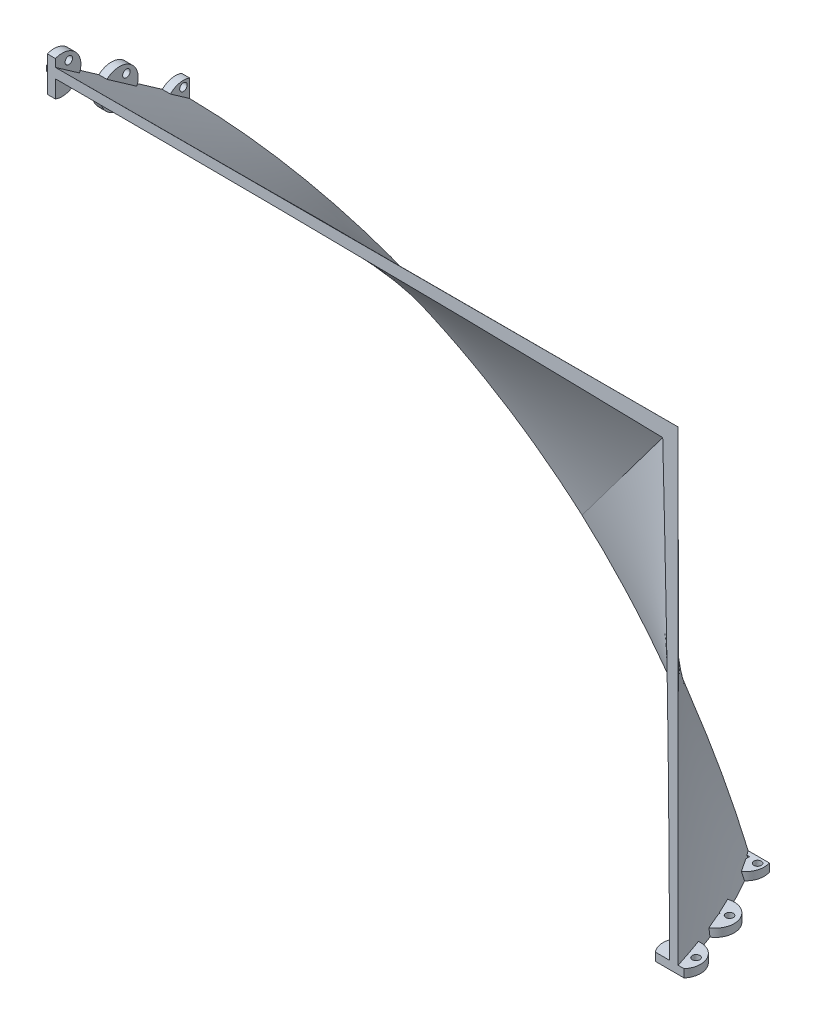
SolidWorks part; units mm, degrees
ref_plane "Plan de face" through (0, 0, 0) normal (0, 0, 1) x (1, 0, 0)
ref_plane "Plan de dessus" through (0, 0, 0) normal (0, 1, 0) x (1, 0, 0)
ref_plane "Plan de droite" through (0, 0, 0) normal (1, 0, 0) x (0, 0, -1)
ref_plane "Plan1" through (0, 0, 10) normal (0, 0, 1) x (1, 0, 0)
ref_plane "Plan2" through (0, 0, 60) normal (0, 0, 1) x (1, 0, 0)
sketch "Esquisse1" plane through (0, 0, 60) normal (0, 0, 1) x (1, 0, 0)
  line L1 (-235, -265) -> (235, -265)
  line L2 (-235, -265) -> (-235, 265)
  line L3 (-235, 265) -> (235, 265)
  line L4 (235, -265) -> (235, 265)
  line L5 (-235, -265) -> (235, 265) construction
  line L6 (-235, 265) -> (235, -265) construction
  point P0 (0, 0)
  dimension "D1" = 470
  dimension "D2" = 530
sketch "Esquisse2" plane through (0, 0, 10) normal (0, 0, 1) x (1, 0, 0)
  circle A0 centre (0, 0) radius 230
loft "Lissage1" add profiles "Esquisse2", "Esquisse1" connector at (-217.3645, 75.1842, 10) connector at (-235, 265, 60)
shell "Coque1" thickness 3 removed face at (0, 0, 60)
sketch "Esquisse3" plane through (0, 0, 13) normal (0, 0, 1) x (1, 0, 0)
  spline S4 degree 3 poles (-1744.7327, 376.1903) (-526.9338, -261.2431) (-3.804, -346.9049) (174.7035, -148.6101) (179.7346, -142.3812) (189.1199, -129.386) (193.4749, -122.6201) (198.4789, -113.8135) (199.4591, -112.0321) (201.3646, -108.4534) (202.2908, -106.6549) (204.9907, -101.232) (206.6856, -97.5804) (211.4617, -86.5187) (214.236, -79.0024) (218.9895, -63.6942) (220.9703, -55.9031) (222.9555, -45.9941) (223.3279, -44.0038) (224.0237, -40.0062) (224.3459, -38.0049) (225.2353, -32.0028) (225.7261, -28) (226.8998, -15.9875) (227.2865, -7.9737) (227.2836, 8.0646) (226.894, 16.0892) (225.9081, 26.1268) (225.6858, 28.1347) (225.1902, 32.1512) (224.9166, 34.1622) (224.021, 40.178) (223.3259, 44.156) (220.9479, 55.9928) (218.9722, 63.7545) (214.2305, 79.0156) (211.4628, 86.5145) (206.6954, 97.5584) (205.0032, 101.2055) (202.3067, 106.6237) (201.3815, 108.421) (199.4777, 111.9979) (198.4976, 113.78) (193.4909, 122.5945) (189.1338, 129.3656) (179.7439, 142.3695) (174.7107, 148.6017) (-4.1787, 347.3344) (-528.7451, 260.2995) (-1744.2878, -377.4815) knots -1.953743 -1.953743 -1.953743 -1.953743 0.0625 0.0625 0.125 0.125 0.1875 0.1875 0.203125 0.203125 0.21875 0.21875 0.25 0.25 0.3125 0.3125 0.375 0.375 0.390625 0.390625 0.40625 0.40625 0.4375 0.4375 0.5 0.5 0.5625 0.5625 0.578125 0.578125 0.59375 0.59375 0.625 0.625 0.6875 0.6875 0.75 0.75 0.78125 0.78125 0.796875 0.796875 0.8125 0.8125 0.875 0.875 0.9375 0.9375 2.957415 2.957415 2.957415 2.957415 only from (152.2162, -171.6485) to (152.2162, 171.6485)
  spline S5 degree 3 poles (-195.2618, -1771.3819) (316.1646, -491.0086) (344.6975, 32.7076) (130.3839, 188.7229) (124.6273, 192.5237) (112.7752, 199.5943) (106.68, 202.8645) (98.8449, 206.6138) (97.2671, 207.3467) (94.0897, 208.7785) (92.4898, 209.4774) (87.681, 211.5127) (84.4552, 212.7913) (74.7194, 216.3971) (68.1511, 218.4952) (54.8632, 222.0955) (48.1436, 223.5983) (34.5539, 226.0114) (27.684, 226.9224) (19.0006, 227.6836) (17.263, 227.8166) (13.7931, 228.0438) (12.0597, 228.1381) (6.8641, 228.3641) (3.4064, 228.4387) (-6.9486, 228.4367) (-13.828, 228.1355) (-27.5391, 226.9367) (-34.3709, 226.0386) (-44.5819, 224.2333) (-47.9794, 223.5547) (-53.0663, 222.4195) (-54.7604, 222.0216) (-58.1454, 221.1859) (-59.8336, 220.7489) (-68.2258, 218.4749) (-74.8099, 216.3655) (-87.7243, 211.5786) (-94.0544, 208.9004) (-106.4603, 202.9753) (-112.536, 199.7278) (-121.4549, 194.4207) (-124.3952, 192.5788) (-128.7561, 189.7046) (-130.2026, 188.7271) (-133.0695, 186.7413) (-134.4907, 185.7324) (-375.502, 10.4249) (-260.223, -622.6751) (244.4446, -1759.2058) knots -2.272579 -2.272579 -2.272579 -2.272579 0.0625 0.0625 0.125 0.125 0.1875 0.1875 0.203125 0.203125 0.21875 0.21875 0.25 0.25 0.3125 0.3125 0.375 0.375 0.4375 0.4375 0.453125 0.453125 0.46875 0.46875 0.5 0.5 0.5625 0.5625 0.625 0.625 0.65625 0.65625 0.671875 0.671875 0.6875 0.6875 0.75 0.75 0.8125 0.8125 0.875 0.875 0.90625 0.90625 0.921875 0.921875 0.9375 0.9375 3.594862 3.594862 3.594862 3.594862 only from (152.2162, 171.6485) to (-152.2162, 171.6485)
  spline S6 degree 3 poles (1744.7327, -376.1903) (526.9338, 261.2431) (3.804, 346.9049) (-174.7035, 148.6101) (-179.7346, 142.3812) (-189.1199, 129.386) (-193.4749, 122.6201) (-198.4789, 113.8135) (-199.4591, 112.0321) (-201.3646, 108.4534) (-202.2908, 106.6549) (-204.9907, 101.232) (-206.6856, 97.5804) (-211.4617, 86.5187) (-214.236, 79.0024) (-218.9895, 63.6942) (-220.9703, 55.9031) (-222.9555, 45.9941) (-223.3279, 44.0038) (-224.0237, 40.0062) (-224.3459, 38.0049) (-225.2353, 32.0028) (-225.7261, 28) (-226.8998, 15.9875) (-227.2865, 7.9737) (-227.2836, -8.0646) (-226.894, -16.0892) (-225.9081, -26.1268) (-225.6858, -28.1347) (-225.1902, -32.1512) (-224.9166, -34.1622) (-224.021, -40.178) (-223.3259, -44.156) (-220.9479, -55.9928) (-218.9722, -63.7545) (-214.2305, -79.0156) (-211.4628, -86.5145) (-206.6954, -97.5584) (-205.0032, -101.2055) (-202.3067, -106.6237) (-201.3815, -108.421) (-199.4777, -111.9979) (-198.4976, -113.78) (-193.4909, -122.5945) (-189.1338, -129.3656) (-179.7439, -142.3695) (-174.7107, -148.6017) (4.1787, -347.3344) (528.7451, -260.2995) (1744.2878, 377.4815) knots -1.953743 -1.953743 -1.953743 -1.953743 0.0625 0.0625 0.125 0.125 0.1875 0.1875 0.203125 0.203125 0.21875 0.21875 0.25 0.25 0.3125 0.3125 0.375 0.375 0.390625 0.390625 0.40625 0.40625 0.4375 0.4375 0.5 0.5 0.5625 0.5625 0.578125 0.578125 0.59375 0.59375 0.625 0.625 0.6875 0.6875 0.75 0.75 0.78125 0.78125 0.796875 0.796875 0.8125 0.8125 0.875 0.875 0.9375 0.9375 2.957415 2.957415 2.957415 2.957415 only from (-152.2162, 171.6485) to (-152.2162, -171.6485)
  spline S7 degree 3 poles (195.2618, 1771.3819) (-316.1646, 491.0086) (-344.6975, -32.7076) (-130.3839, -188.7229) (-124.6273, -192.5237) (-112.7752, -199.5943) (-106.68, -202.8645) (-98.8449, -206.6138) (-97.2671, -207.3467) (-94.0897, -208.7785) (-92.4898, -209.4774) (-87.681, -211.5127) (-84.4552, -212.7913) (-74.7194, -216.3971) (-68.1511, -218.4952) (-54.8632, -222.0955) (-48.1436, -223.5983) (-34.5539, -226.0114) (-27.684, -226.9224) (-19.0006, -227.6836) (-17.263, -227.8166) (-13.7931, -228.0438) (-12.0597, -228.1381) (-6.8641, -228.3641) (-3.4064, -228.4387) (6.9486, -228.4367) (13.828, -228.1355) (27.5391, -226.9367) (34.3709, -226.0386) (44.5819, -224.2333) (47.9794, -223.5547) (53.0663, -222.4195) (54.7604, -222.0216) (58.1454, -221.1859) (59.8336, -220.7489) (68.2258, -218.4749) (74.8099, -216.3655) (87.7243, -211.5786) (94.0544, -208.9004) (106.4603, -202.9753) (112.536, -199.7278) (121.4549, -194.4207) (124.3952, -192.5788) (128.7561, -189.7046) (130.2026, -188.7271) (133.0695, -186.7413) (134.4907, -185.7324) (375.502, -10.4249) (260.223, 622.6751) (-244.4446, 1759.2058) knots -2.272579 -2.272579 -2.272579 -2.272579 0.0625 0.0625 0.125 0.125 0.1875 0.1875 0.203125 0.203125 0.21875 0.21875 0.25 0.25 0.3125 0.3125 0.375 0.375 0.4375 0.4375 0.453125 0.453125 0.46875 0.46875 0.5 0.5 0.5625 0.5625 0.625 0.625 0.65625 0.65625 0.671875 0.671875 0.6875 0.6875 0.75 0.75 0.8125 0.8125 0.875 0.875 0.90625 0.90625 0.921875 0.921875 0.9375 0.9375 3.594862 3.594862 3.594862 3.594862 only from (-152.2162, -171.6485) to (152.2162, -171.6485)
  spline S8 degree 3 poles (152.2162, -171.6485) (158.2661, -166.2289) (163.9694, -160.534) (174.7035, -148.6101) (179.7346, -142.3812) (189.1199, -129.386) (193.4749, -122.6201) (198.4789, -113.8135) (199.4591, -112.0321) (201.3646, -108.4534) (202.2908, -106.6549) (204.9907, -101.232) (206.6856, -97.5804) (211.4617, -86.5187) (214.236, -79.0024) (218.9895, -63.6942) (220.9703, -55.9031) (222.9555, -45.9941) (223.3279, -44.0038) (224.0237, -40.0062) (224.3459, -38.0049) (225.2353, -32.0028) (225.7261, -28) (226.8998, -15.9875) (227.2865, -7.9737) (227.2836, 8.0646) (226.894, 16.0892) (225.9081, 26.1268) (225.6858, 28.1347) (225.1902, 32.1512) (224.9166, 34.1622) (224.021, 40.178) (223.3259, 44.156) (220.9479, 55.9928) (218.9722, 63.7545) (214.2305, 79.0156) (211.4628, 86.5145) (206.6954, 97.5584) (205.0032, 101.2055) (202.3067, 106.6237) (201.3815, 108.421) (199.4777, 111.9979) (198.4976, 113.78) (193.4909, 122.5945) (189.1338, 129.3656) (179.7439, 142.3695) (174.7107, 148.6017) (163.9726, 160.5309) (158.2675, 166.2277) (152.2162, 171.6485) knots 0 0 0 0 0.0625 0.0625 0.125 0.125 0.1875 0.1875 0.203125 0.203125 0.21875 0.21875 0.25 0.25 0.3125 0.3125 0.375 0.375 0.390625 0.390625 0.40625 0.40625 0.4375 0.4375 0.5 0.5 0.5625 0.5625 0.578125 0.578125 0.59375 0.59375 0.625 0.625 0.6875 0.6875 0.75 0.75 0.78125 0.78125 0.796875 0.796875 0.8125 0.8125 0.875 0.875 0.9375 0.9375 1 1 1 1
  spline S9 degree 3 poles (152.2162, 171.6485) (146.9741, 176.2555) (141.5573, 180.5889) (130.3839, 188.7229) (124.6273, 192.5237) (112.7752, 199.5943) (106.68, 202.8645) (98.8449, 206.6138) (97.2671, 207.3467) (94.0897, 208.7785) (92.4898, 209.4774) (87.681, 211.5127) (84.4552, 212.7913) (74.7194, 216.3971) (68.1511, 218.4952) (54.8632, 222.0955) (48.1436, 223.5983) (34.5539, 226.0114) (27.684, 226.9224) (19.0006, 227.6836) (17.263, 227.8166) (13.7931, 228.0438) (12.0597, 228.1381) (6.8641, 228.3641) (3.4064, 228.4387) (-6.9486, 228.4367) (-13.828, 228.1355) (-27.5391, 226.9367) (-34.3709, 226.0386) (-44.5819, 224.2333) (-47.9794, 223.5547) (-53.0663, 222.4195) (-54.7604, 222.0216) (-58.1454, 221.1859) (-59.8336, 220.7489) (-68.2258, 218.4749) (-74.8099, 216.3655) (-87.7243, 211.5786) (-94.0544, 208.9004) (-106.4603, 202.9753) (-112.536, 199.7278) (-121.4549, 194.4207) (-124.3952, 192.5788) (-128.7561, 189.7046) (-130.2026, 188.7271) (-133.0695, 186.7413) (-134.4907, 185.7324) (-141.5348, 180.6086) (-146.9739, 176.2557) (-152.2162, 171.6485) knots 0 0 0 0 0.0625 0.0625 0.125 0.125 0.1875 0.1875 0.203125 0.203125 0.21875 0.21875 0.25 0.25 0.3125 0.3125 0.375 0.375 0.4375 0.4375 0.453125 0.453125 0.46875 0.46875 0.5 0.5 0.5625 0.5625 0.625 0.625 0.65625 0.65625 0.671875 0.671875 0.6875 0.6875 0.75 0.75 0.8125 0.8125 0.875 0.875 0.90625 0.90625 0.921875 0.921875 0.9375 0.9375 1 1 1 1
  spline S10 degree 3 poles (-152.2162, 171.6485) (-158.2661, 166.2289) (-163.9694, 160.534) (-174.7035, 148.6101) (-179.7346, 142.3812) (-189.1199, 129.386) (-193.4749, 122.6201) (-198.4789, 113.8135) (-199.4591, 112.0321) (-201.3646, 108.4534) (-202.2908, 106.6549) (-204.9907, 101.232) (-206.6856, 97.5804) (-211.4617, 86.5187) (-214.236, 79.0024) (-218.9895, 63.6942) (-220.9703, 55.9031) (-222.9555, 45.9941) (-223.3279, 44.0038) (-224.0237, 40.0062) (-224.3459, 38.0049) (-225.2353, 32.0028) (-225.7261, 28) (-226.8998, 15.9875) (-227.2865, 7.9737) (-227.2836, -8.0646) (-226.894, -16.0892) (-225.9081, -26.1268) (-225.6858, -28.1347) (-225.1902, -32.1512) (-224.9166, -34.1622) (-224.021, -40.178) (-223.3259, -44.156) (-220.9479, -55.9928) (-218.9722, -63.7545) (-214.2305, -79.0156) (-211.4628, -86.5145) (-206.6954, -97.5584) (-205.0032, -101.2055) (-202.3067, -106.6237) (-201.3815, -108.421) (-199.4777, -111.9979) (-198.4976, -113.78) (-193.4909, -122.5945) (-189.1338, -129.3656) (-179.7439, -142.3695) (-174.7107, -148.6017) (-163.9726, -160.5309) (-158.2675, -166.2277) (-152.2162, -171.6485) knots 0 0 0 0 0.0625 0.0625 0.125 0.125 0.1875 0.1875 0.203125 0.203125 0.21875 0.21875 0.25 0.25 0.3125 0.3125 0.375 0.375 0.390625 0.390625 0.40625 0.40625 0.4375 0.4375 0.5 0.5 0.5625 0.5625 0.578125 0.578125 0.59375 0.59375 0.625 0.625 0.6875 0.6875 0.75 0.75 0.78125 0.78125 0.796875 0.796875 0.8125 0.8125 0.875 0.875 0.9375 0.9375 1 1 1 1
  spline S11 degree 3 poles (-152.2162, -171.6485) (-146.9741, -176.2555) (-141.5573, -180.5889) (-130.3839, -188.7229) (-124.6273, -192.5237) (-112.7752, -199.5943) (-106.68, -202.8645) (-98.8449, -206.6138) (-97.2671, -207.3467) (-94.0897, -208.7785) (-92.4898, -209.4774) (-87.681, -211.5127) (-84.4552, -212.7913) (-74.7194, -216.3971) (-68.1511, -218.4952) (-54.8632, -222.0955) (-48.1436, -223.5983) (-34.5539, -226.0114) (-27.684, -226.9224) (-19.0006, -227.6836) (-17.263, -227.8166) (-13.7931, -228.0438) (-12.0597, -228.1381) (-6.8641, -228.3641) (-3.4064, -228.4387) (6.9486, -228.4367) (13.828, -228.1355) (27.5391, -226.9367) (34.3709, -226.0386) (44.5819, -224.2333) (47.9794, -223.5547) (53.0663, -222.4195) (54.7604, -222.0216) (58.1454, -221.1859) (59.8336, -220.7489) (68.2258, -218.4749) (74.8099, -216.3655) (87.7243, -211.5786) (94.0544, -208.9004) (106.4603, -202.9753) (112.536, -199.7278) (121.4549, -194.4207) (124.3952, -192.5788) (128.7561, -189.7046) (130.2026, -188.7271) (133.0695, -186.7413) (134.4907, -185.7324) (141.5348, -180.6086) (146.9739, -176.2557) (152.2162, -171.6485) knots 0 0 0 0 0.0625 0.0625 0.125 0.125 0.1875 0.1875 0.203125 0.203125 0.21875 0.21875 0.25 0.25 0.3125 0.3125 0.375 0.375 0.4375 0.4375 0.453125 0.453125 0.46875 0.46875 0.5 0.5 0.5625 0.5625 0.625 0.625 0.65625 0.65625 0.671875 0.671875 0.6875 0.6875 0.75 0.75 0.8125 0.8125 0.875 0.875 0.90625 0.90625 0.921875 0.921875 0.9375 0.9375 1 1 1 1
  dimension "D1" = 0
extrude "Enlèv. mat.-Extru.1" cut sketch "Esquisse3" against normal blind 10
sketch "Esquisse4" plane through (0, 0, 0) normal (0, 1, 0) x (1, 0, 0)
  line L0 (-55, -10) -> (55, -10) construction
  line L1 (-235, -10) -> (235, -10)
  line L2 (-235, -10) -> (-235, -60)
  line L3 (-235, -60) -> (235, -60)
  line L4 (235, -10) -> (235, -60)
  line L5 (-55, -60) -> (55, -60) construction
  line L6 (0, -10) -> (0, -60)
  point P10 (0, -60)
  point P13 (0, -10)
extrude "Enlèv. mat.-Extru.2" cut sketch "Esquisse4" against normal through all both and the other way through all contours L6 L1 L2 L3 region at (-117.5, 0, 35)
sketch "Esquisse7" plane through (0, 0, 0) normal (0, 0, 1) x (1, 0, 0)
  line L0 (0, -88.3333) -> (235, -88.3333)
  line L1 (0, 261.338) -> (235, 261.338)
  line L2 (0, 261.338) -> (0, -265)
  line L3 (0, -265) -> (235, -265)
  line L4 (235, 261.338) -> (235, -265)
  line L5 (0, 88.3333) -> (235, 88.3333)
  dimension "D1" = 176.6667
  dimension "D2" = 176.6667
extrude "Enlèv. mat.-Extru.3" cut sketch "Esquisse7" against normal through all both and the other way through all contours L4 L0 L2 L3 | L5 L2 L0 L4 region at (117.5, 0, 0) region at (117.5, -176.6667, 0)
sketch "Esquisse8" plane through (0, 88.3333, 0) normal (0, -1, 0) x (1, 0, 0)
  line L0 (225, 36.15) -> (225, 60) construction
  line L1 (224, 35.4) -> (226, 35.4)
  line L2 (224, 35.4) -> (224, 36.9)
  line L3 (224, 36.9) -> (226, 36.9)
  line L4 (226, 35.4) -> (226, 36.9)
  line L5 (224, 35.4) -> (226, 36.9) construction
  line L6 (224, 36.9) -> (226, 35.4) construction
  line L7 (97.1744, 60) -> (-97.1744, 60) construction
  line L8 (225, 60) -> (235, 60) construction
  line L10 (235, 60) -> (235, 36.15) construction
  line L11 (231.8645, 55.5) -> (235.8645, 55.5) construction
  line L12 (231.8645, 60) -> (231.8645, 55.5) construction
  line L13 (212.361, 10) -> (212.361, 12.3) construction
  line L14 (205.7497, 10) -> (218.9724, 10)
  line L15 (230.8645, 54.75) -> (232.8645, 54.75)
  line L16 (230.8645, 54.75) -> (230.8645, 56.25)
  line L17 (230.8645, 56.25) -> (232.8645, 56.25)
  line L18 (232.8645, 54.75) -> (232.8645, 56.25)
  line L19 (230.8645, 54.75) -> (232.8645, 56.25) construction
  line L20 (230.8645, 56.25) -> (232.8645, 54.75) construction
  line L21 (211.461, 11.65) -> (213.261, 11.65)
  line L22 (211.461, 11.65) -> (211.461, 12.95)
  line L23 (211.461, 12.95) -> (213.261, 12.95)
  line L24 (213.261, 11.65) -> (213.261, 12.95)
  line L25 (211.461, 11.65) -> (213.261, 12.95) construction
  line L26 (211.461, 12.95) -> (213.261, 11.65) construction
  line L27 (152.2162, 10) -> (210.59, 10) construction
  line L28 (97.1744, 10) -> (-97.1744, 10) construction
  line L29 (226.5026, 60) -> (237.2264, 60)
  line L30 (238.3714, 53.3767) -> (225.0703, 57.7448) construction
  line L31 (235, 60) -> (231.2328, 48.5286) construction
  line L32 (230.9261, 33.3126) -> (218.0536, 38.8171) construction
  line L33 (228.8555, 41.9925) -> (223.4391, 29.3262) construction
  line L34 (217.1315, 17.4228) -> (212.361, 10) construction
  line L35 (212.361, 12.3) -> (216.891, 12.3) construction
  line L36 (225, 36.15) -> (228.5, 36.15) construction
  line L37 (228.5, 36.15) -> (228.5, 34.35) construction
  line L38 (235.8645, 55.5) -> (235.8645, 54.2) construction
  arc A0 (226.5026, 60) -> (237.2264, 60) centre (231.8645, 55.5) ccw
  circle A1 centre (225, 36.15) radius 7
  arc A2 (218.9724, 10) -> (205.7497, 10) centre (212.361, 12.3) ccw
  arc A3 (205.7497, 10) -> (218.9724, 10) centre (212.361, 12.3) ccw construction
  arc A4 (237.2264, 60) -> (226.5026, 60) centre (231.8645, 55.5) ccw construction
  circle A5 centre (235.8645, 54.2) radius 1.4
  circle A6 centre (228.5, 34.35) radius 1.4
  circle A7 centre (216.891, 12.3) radius 1.4
  spline S0 degree 3 poles (212.361, 10) (214.9908, 13.7747) (217.3789, 17.6908) (220.6719, 23.734) (221.7217, 25.7777) (223.733, 29.9109) (225.6529, 34.0835) (227.4125, 38.3253) (229.1017, 42.5976) (229.9111, 44.7493) (232.2428, 51.2344) (233.6703, 55.6006) (235, 60) knots 0 0 0 0 0.25 0.25 0.375 0.375 0.5 0.625 0.625 0.75 0.75 1 1 1 1 construction
  point P0 (225, 36.15)
  point P41 (231.2328, 48.5286)
  point P42 (223.4391, 29.3262)
  point P51 (228.8555, 41.9925)
  point P59 (216.8065, 17.7072)
  dimension "D11" = 4
  dimension "D12" = 2.8
  dimension "D14" = 2.8
  dimension "D16" = 2.8
  dimension "D17" = 4.53
  dimension "D1" = 2
  dimension "D2" = 1.5
  dimension "D3" = 23.85
  dimension "D4" = 10
  dimension "D6" = 4.5
  dimension "D7" = 1.8
  dimension "D8" = 1.3
  dimension "D9" = 2
  dimension "D10" = 1.5
  dimension "D13" = 3.5
  dimension "D15" = 1.8
  dimension "D18" = 1.3
extrude "Boss.-Extru.1" add sketch "Esquisse8" along normal blind 2 contours L22 L21 L24 L23 | L2 L1 L4 L3 | L16 L15 L18 L17
sketch "Esquisse9" plane through (0, 0, 0) normal (-1, 0, 0) x (0, 0, 1)
  line L0 (60, 261.338) -> (57.5, 261.338) construction
  line L1 (60, -97.1744) -> (60, 97.1744) construction
  line L2 (60, 246.338) -> (36.15, 246.338) construction
  line L3 (36.9, 247.338) -> (35.4, 247.338)
  line L4 (36.9, 247.338) -> (36.9, 245.338)
  line L5 (36.9, 245.338) -> (35.4, 245.338)
  line L6 (35.4, 247.338) -> (35.4, 245.338)
  line L7 (36.9, 247.338) -> (35.4, 245.338) construction
  line L8 (36.9, 245.338) -> (35.4, 247.338) construction
  line L9 (10, 230) -> (12.3, 230) construction
  line L10 (60, 267.8764) -> (60, 254.7997)
  line L11 (11.65, 230.9) -> (12.95, 230.9)
  line L12 (11.65, 230.9) -> (11.65, 229.1)
  line L13 (11.65, 229.1) -> (12.95, 229.1)
  line L14 (12.95, 230.9) -> (12.95, 229.1)
  line L15 (11.65, 230.9) -> (12.95, 229.1) construction
  line L16 (11.65, 229.1) -> (12.95, 230.9) construction
  line L17 (56.75, 260.338) -> (58.25, 260.338)
  line L18 (56.75, 260.338) -> (56.75, 262.338)
  line L19 (56.75, 262.338) -> (58.25, 262.338)
  line L20 (58.25, 260.338) -> (58.25, 262.338)
  line L21 (56.75, 260.338) -> (58.25, 262.338) construction
  line L22 (56.75, 262.338) -> (58.25, 260.338) construction
  line L23 (60, 261.338) -> (60, 265) construction
  line L24 (10, 236.6114) -> (10, 223.3886)
  line L25 (10, -97.1744) -> (10, 97.1744) construction
  line L26 (10, 228.438) -> (10, 171.6485) construction
  line L27 (12.3, 230) -> (12.3, 234.8) construction
  line L28 (10, 230) -> (60, 265) construction
  line L29 (29.6453, 243.7517) -> (40.8065, 251.5646) construction
  line L30 (36.15, 246.338) -> (36.15, 249.838) construction
  line L31 (51.0125, 258.7088) -> (62.1665, 266.4789) construction
  line L33 (5.9161, 227.1284) -> (17.1755, 235.0229) construction
  line L34 (57.5, 261.338) -> (57.5, 264.838) construction
  line L35 (57.5, 264.838) -> (55, 264.838) construction
  line L36 (36.15, 249.838) -> (33.55, 249.838) construction
  arc A0 (60, 267.8764) -> (60, 254.7997) centre (57.5, 261.338) ccw
  circle A1 centre (36.15, 246.338) radius 7
  arc A2 (10, 223.3886) -> (10, 236.6114) centre (12.3, 230) ccw
  arc A3 (60, 254.7997) -> (60, 267.8764) centre (57.5, 261.338) ccw construction
  arc A4 (10, 236.6114) -> (10, 223.3886) centre (12.3, 230) ccw construction
  circle A5 centre (33.55, 249.838) radius 1.4
  circle A6 centre (55, 264.838) radius 1.4
  circle A7 centre (12.3, 234.8) radius 1.4
  point P2 (51.0125, 258.7088)
  point P54 (17.1755, 235.0229)
  dimension "D11" = 2.6
  dimension "D12" = 2.8
  dimension "D14" = 2.8
  dimension "D16" = 2.8
  dimension "D17" = 3.5
  dimension "D1" = 15
  dimension "D2" = 23.85
  dimension "D3" = 2
  dimension "D4" = 1.5
  dimension "D5" = 2.3
  dimension "D6" = 1.8
  dimension "D7" = 1.3
  dimension "D8" = 2.5
  dimension "D9" = 2
  dimension "D10" = 1.5
  dimension "D13" = 2.75
  dimension "D15" = 4.8
  dimension "D18" = 2.5
  dimension "D19" = 3.5
extrude "Boss.-Extru.2" add sketch "Esquisse9" along normal blind 2 contours L12 L11 L14 L13 | L4 L3 L6 L5 | L18 L17 L20 L19
extrude "Boss.-Extru.3" add sketch "Esquisse8<3>" against normal blind 3
sketch "Esquisse8<3>" plane through (0, 88.3333, 0) normal (0, -1, 0) x (1, 0, 0) same geometry as "Esquisse8"
extrude "Boss.-Extru.4" add sketch "Esquisse9<3>" against normal blind 3
sketch "Esquisse9<3>" plane through (0, 0, 0) normal (-1, 0, 0) x (0, 0, 1) same geometry as "Esquisse9"
